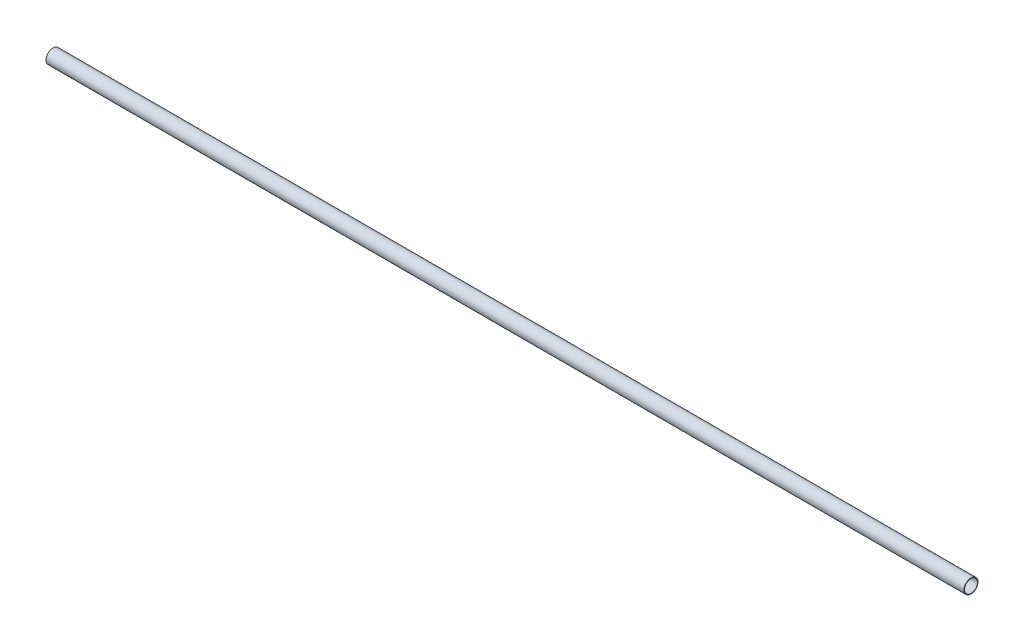
SolidWorks part; units mm, degrees
ref_plane "Front Plane" through (0, 0, 0) normal (0, 0, 1) x (1, 0, 0)
ref_plane "Top Plane" through (0, 0, 0) normal (0, 1, 0) x (1, 0, 0)
ref_plane "Right Plane" through (0, 0, 0) normal (1, 0, 0) x (0, 0, -1)
sketch "Sketch1" plane through (0, 0, 0) normal (1, 0, 0) x (0, 0, -1)
  circle A0 centre (0, 0) radius 13
  circle A1 centre (0, 0) radius 12
  dimension "D1" = 26
  dimension "D2" = 24
extrude "Boss-Extrude1" add sketch "Sketch1" along normal blind 1700
